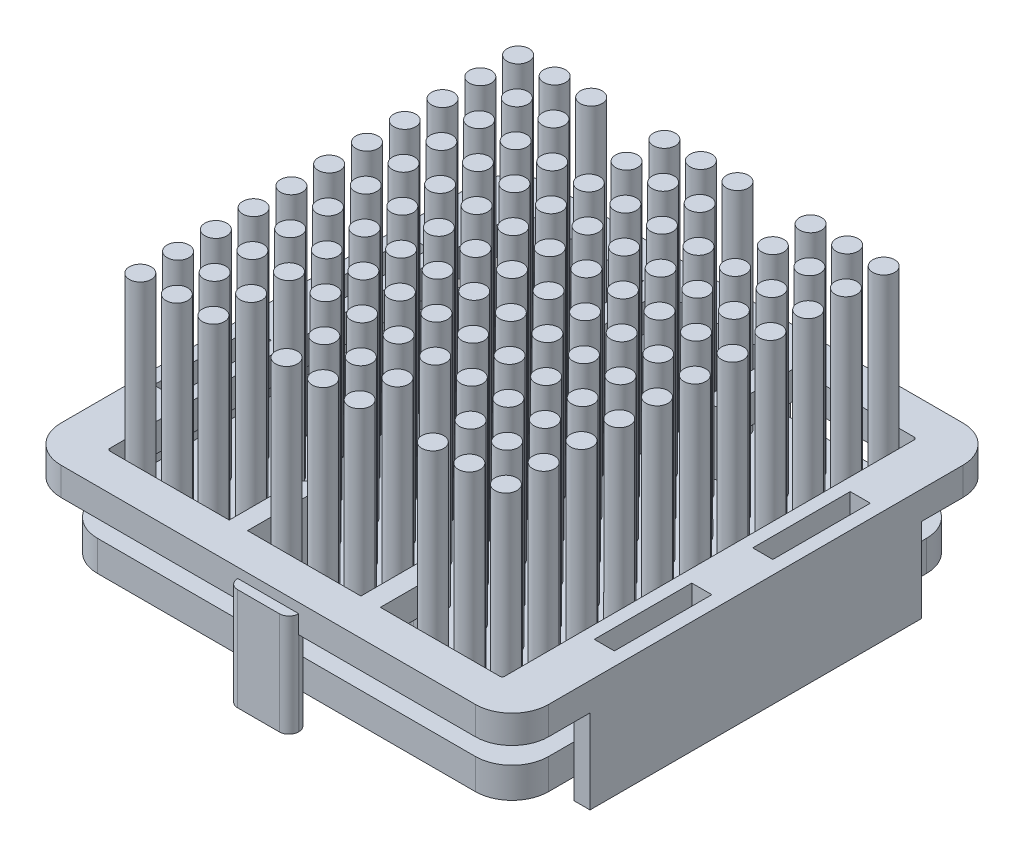
SolidWorks part; units mm, degrees
ref_plane "Alzado" through (0, 0, 0) normal (0, 0, 1) x (1, 0, 0)
ref_plane "Planta" through (0, 0, 0) normal (0, 1, 0) x (1, 0, 0)
ref_plane "Vista lateral" through (0, 0, 0) normal (1, 0, 0) x (0, 0, -1)
sketch "Croquis1" plane through (0, 0, 0) normal (0, 1, 0) x (1, 0, 0)
  line L1 (-20, 20) -> (20, 20)
  line L2 (-20, 20) -> (-20, -20)
  line L3 (-20, -20) -> (20, -20)
  line L4 (20, 20) -> (20, -20)
  dimension "D1" = 40
  dimension "D2" = 40
  dimension "D3" = 20
  dimension "D4" = 20
extrude "Extruir1" add sketch "Croquis1" along normal blind 9.2
sketch "Croquis2" plane through (0, 9.2, 0) normal (0, 1, 0) x (1, 0, 0)
  line L0 (20, 20) -> (-20, 20) construction
  line L1 (-16.2, 17) -> (-6.2, 17)
  line L2 (-16.2, 17) -> (-16.2, -17)
  line L3 (-16.2, -17) -> (-6.2, -17)
  line L4 (16.2, 17) -> (16.2, -17)
  line L5 (-4.7, 17) -> (4.6, 17)
  line L6 (-6.2, 17) -> (-6.2, 11)
  line L8 (-4.7, 17) -> (-4.7, 11)
  line L9 (6.2, 17) -> (16.2, 17)
  line L10 (4.6, 17) -> (4.6, 11)
  line L12 (6.2, 17) -> (6.2, 11)
  line L13 (-6.2, 11) -> (-4.7, 11)
  line L14 (4.6, -11) -> (6.2, -11)
  line L15 (-6.2, -11) -> (-4.7, -11)
  line L16 (-4.7, -17) -> (4.6, -17)
  line L17 (-20, -20) -> (20, -20) construction
  line L18 (-6.2, -11) -> (-6.2, -17)
  line L19 (-4.7, -11) -> (-4.7, -17)
  line L20 (4.6, -11) -> (4.6, -17)
  line L21 (6.2, -11) -> (6.2, -17)
  line L22 (4.6, 11) -> (6.2, 11)
  line L23 (6.2, -17) -> (16.2, -17)
  dimension "D1" = 32.4
  dimension "D2" = 16.2
  dimension "D3" = 34
  dimension "D4" = 17
  dimension "D5" = 9.3
  dimension "D6" = 12.4
  dimension "D7" = 6.2
  dimension "D8" = 1.5
  dimension "D9" = 9
  dimension "D10" = 9
extrude "Cortar-Extruir1" cut sketch "Croquis2" against normal blind 16.2
fillet "Redondeo1" radius 3 4 edges at (20, 4.6, -20) (20, 4.6, 20) (-20, 4.6, 20) (-20, 4.6, -20)
fillet "Redondeo2" radius 0.2 4 edges at (-16.2, 4.6, -17) (16.2, 4.6, -17) (-16.2, 4.6, 17) (16.2, 4.6, 17)
sketch "Croquis3" plane through (-20, 0, 0) normal (-1, 0, 0) x (0, 0, 1)
  line L0 (-17, 9.2) -> (17, 9.2) construction
  line L1 (-24.4068, 6.9) -> (-13.6, 6.9)
  line L2 (-24.4068, 6.9) -> (-24.4068, -1.7629)
  line L3 (-24.4068, -1.7629) -> (-13.6, -1.7629)
  line L4 (-13.6, 6.9) -> (-13.6, -1.7629)
  line L5 (13.6, 6.9) -> (26.4688, 6.9)
  line L6 (13.6, 6.9) -> (13.6, -1.7629)
  line L7 (13.6, -1.7629) -> (26.4688, -1.7629)
  line L8 (26.4688, 6.9) -> (26.4688, -1.7629)
  dimension "D1" = 27.2
  dimension "D2" = 2.3
  dimension "D3" = 13.6
extrude "Cortar-Extruir2" cut sketch "Croquis3" against normal blind 58.2
sketch "Croquis4" plane through (0, 0, -20) normal (0, 0, -1) x (-1, 0, 0)
  line L0 (-20, 6.9) -> (-17, 6.9) construction
  line L1 (-18.7, 6.9) -> (-11.7389, 6.9)
  line L2 (-18.7, 6.9) -> (-18.7, -3.2782)
  line L3 (-18.7, -3.2782) -> (-11.7389, -3.2782)
  line L4 (18.7, 6.9) -> (18.7, -3.2782)
  line L5 (11.3622, -3.2782) -> (18.7, -3.2782)
  line L7 (-11.7389, 6.9) -> (-11.7389, -3.2782)
  line L9 (11.3622, 6.9) -> (11.3622, -3.2782)
  line L10 (11.3622, 6.9) -> (18.7, 6.9)
  dimension "D1" = 37.4
  dimension "D2" = 18.7
extrude "Cortar-Extruir3" cut sketch "Croquis4" against normal blind 58.2
fillet "Redondeo3" radius 0.7 16 edges at (4.6, 3.45, 13.6) (6.2, 3.45, 13.6) (6.2, 4.6, 11) (4.6, 4.6, 11) (-4.7, 3.45, 13.6) (-4.7, 4.6, 11) (-6.2, 4.6, 11) (-6.2, 3.45, 13.6) (-6.2, 4.6, -11) (-6.2, 3.45, -13.6) (-4.7, 3.45, -13.6) (-4.7, 4.6, -11) (4.6, 3.45, -13.6) (6.2, 3.45, -13.6) (4.6, 4.6, -11) (6.2, 4.6, -11)
ref_plane "Plano1" through (0, 1.5, 0) normal (0, -1, 0) x (1, 0, 0)
sketch "Croquis5" plane through (0, 1.5, 0) normal (0, -1, 0) x (1, 0, 0)
  line L1 (-18.5, 18.5) -> (18.5, 18.5)
  line L2 (-18.5, 18.5) -> (-18.5, -18.5)
  line L3 (-18.5, -18.5) -> (18.5, -18.5)
  line L4 (18.5, 18.5) -> (18.5, -18.5)
  dimension "D1" = 37
  dimension "D2" = 37
  dimension "D3" = 18.5
  dimension "D4" = 18.5
extrude "Extruir2" add sketch "Croquis5" against normal blind 2.5 separate body
fillet "Redondeo4" radius 3 4 edges at (18.5, 2.75, -18.5) (-18.5, 2.75, -18.5) (18.5, 2.75, 18.5) (-18.5, 2.75, 18.5)
sketch "Croquis6" plane through (0, 4, 0) normal (0, 1, 0) x (1, 0, 0)
  line L0 (0, 0) -> (-24.1439, 0) construction
  line L1 (0, 0) -> (0, -22.8603) construction
  circle A0 centre (0, 0) radius 0.9
  circle A1 centre (3, 0) radius 0.9
  circle A2 centre (6, 0) radius 0.9
  circle A3 centre (9, 0) radius 0.9
  circle A4 centre (12, 0) radius 0.9
  circle A5 centre (15, 0) radius 0.9
  circle A6 centre (0, 3.1) radius 0.9
  circle A7 centre (3, 3.1) radius 0.9
  circle A8 centre (6, 3.1) radius 0.9
  circle A9 centre (9, 3.1) radius 0.9
  circle A10 centre (12, 3.1) radius 0.9
  circle A11 centre (15, 3.1) radius 0.9
  circle A12 centre (0, 6.2) radius 0.9
  circle A13 centre (3, 6.2) radius 0.9
  circle A14 centre (6, 6.2) radius 0.9
  circle A15 centre (9, 6.2) radius 0.9
  circle A16 centre (12, 6.2) radius 0.9
  circle A17 centre (15, 6.2) radius 0.9
  circle A18 centre (0, 9.3) radius 0.9
  circle A19 centre (3, 9.3) radius 0.9
  circle A20 centre (6, 9.3) radius 0.9
  circle A21 centre (9, 9.3) radius 0.9
  circle A22 centre (12, 9.3) radius 0.9
  circle A23 centre (15, 9.3) radius 0.9
  circle A24 centre (0, 12.4) radius 0.9
  circle A25 centre (3, 12.4) radius 0.9
  circle A26 centre (-15, 15.5) radius 0.9
  circle A27 centre (9, 12.4) radius 0.9
  circle A28 centre (12, 12.4) radius 0.9
  circle A29 centre (15, 12.4) radius 0.9
  circle A30 centre (0, 15.5) radius 0.9
  circle A31 centre (3, 15.5) radius 0.9
  circle A32 centre (-12, 15.5) radius 0.9
  circle A33 centre (9, 15.5) radius 0.9
  circle A34 centre (12, 15.5) radius 0.9
  circle A35 centre (15, 15.5) radius 0.9
  circle A36 centre (6, 12.4) radius 0.9 [skipped]
  circle A37 centre (6, 15.5) radius 0.9 [skipped]
  circle A38 centre (-9, 15.5) radius 0.9
  circle A39 centre (-3, 15.5) radius 0.9
  circle A40 centre (-15, 12.4) radius 0.9
  circle A41 centre (-12, 12.4) radius 0.9
  circle A42 centre (-9, 12.4) radius 0.9
  circle A43 centre (-3, 12.4) radius 0.9
  circle A44 centre (-15, 9.3) radius 0.9
  circle A45 centre (-12, 9.3) radius 0.9
  circle A46 centre (-9, 9.3) radius 0.9
  circle A47 centre (-6, 9.3) radius 0.9
  circle A48 centre (-3, 9.3) radius 0.9
  circle A49 centre (-15, 6.2) radius 0.9
  circle A50 centre (-12, 6.2) radius 0.9
  circle A51 centre (-9, 6.2) radius 0.9
  circle A52 centre (-6, 6.2) radius 0.9
  circle A53 centre (-3, 6.2) radius 0.9
  circle A54 centre (-15, 3.1) radius 0.9
  circle A55 centre (-12, 3.1) radius 0.9
  circle A56 centre (-9, 3.1) radius 0.9
  circle A57 centre (-6, 3.1) radius 0.9
  circle A58 centre (-3, 3.1) radius 0.9
  circle A59 centre (-15, 0) radius 0.9
  circle A60 centre (-12, 0) radius 0.9
  circle A61 centre (-9, 0) radius 0.9
  circle A62 centre (-6, 0) radius 0.9
  circle A63 centre (-3, 0) radius 0.9
  circle A64 centre (-3, -3.1) radius 0.9
  circle A65 centre (-6, -3.1) radius 0.9
  circle A66 centre (-9, -3.1) radius 0.9
  circle A67 centre (-12, -3.1) radius 0.9
  circle A68 centre (-15, -3.1) radius 0.9
  circle A69 centre (-3, -6.2) radius 0.9
  circle A70 centre (-6, -6.2) radius 0.9
  circle A71 centre (-9, -6.2) radius 0.9
  circle A72 centre (-12, -6.2) radius 0.9
  circle A73 centre (-15, -6.2) radius 0.9
  circle A74 centre (-3, -9.3) radius 0.9
  circle A75 centre (-6, -9.3) radius 0.9
  circle A76 centre (-9, -9.3) radius 0.9
  circle A77 centre (-12, -9.3) radius 0.9
  circle A78 centre (-15, -9.3) radius 0.9
  circle A79 centre (-3, -12.4) radius 0.9
  circle A80 centre (-9, -12.4) radius 0.9
  circle A81 centre (-12, -12.4) radius 0.9
  circle A82 centre (-15, -12.4) radius 0.9
  circle A83 centre (-3, -15.5) radius 0.9
  circle A84 centre (-9, -15.5) radius 0.9
  circle A85 centre (15, -15.5) radius 0.9
  circle A86 centre (12, -15.5) radius 0.9
  circle A87 centre (9, -15.5) radius 0.9
  circle A88 centre (-12, -15.5) radius 0.9
  circle A89 centre (3, -15.5) radius 0.9
  circle A90 centre (0, -15.5) radius 0.9
  circle A91 centre (15, -12.4) radius 0.9
  circle A92 centre (12, -12.4) radius 0.9
  circle A93 centre (9, -12.4) radius 0.9
  circle A94 centre (-15, -15.5) radius 0.9
  circle A95 centre (3, -12.4) radius 0.9
  circle A96 centre (0, -12.4) radius 0.9
  circle A97 centre (15, -9.3) radius 0.9
  circle A98 centre (12, -9.3) radius 0.9
  circle A99 centre (9, -9.3) radius 0.9
  circle A100 centre (6, -9.3) radius 0.9
  circle A101 centre (3, -9.3) radius 0.9
  circle A102 centre (0, -9.3) radius 0.9
  circle A103 centre (15, -6.2) radius 0.9
  circle A104 centre (12, -6.2) radius 0.9
  circle A105 centre (9, -6.2) radius 0.9
  circle A106 centre (6, -6.2) radius 0.9
  circle A107 centre (3, -6.2) radius 0.9
  circle A108 centre (0, -6.2) radius 0.9
  circle A109 centre (15, -3.1) radius 0.9
  circle A110 centre (12, -3.1) radius 0.9
  circle A111 centre (9, -3.1) radius 0.9
  circle A112 centre (6, -3.1) radius 0.9
  circle A113 centre (3, -3.1) radius 0.9
  circle A114 centre (0, -3.1) radius 0.9
  dimension "D1" = 1.8
extrude "Extruir3" add sketch "Croquis6" along normal offset from surface (17.6 mm away) 12.4 separate body up to face at (-0.0188, 9.2, 0) offset beyond the face yes
combine bodies "Combinar1" operation type add bodies to combine 203 201 199 197 136 134 132 130 195 193 191 189 128 126 124 122 187 185 183 181 120 118 116 114 179 177 175 173 112 110 108 106 105 171 169 167 165 163 161 159
sketch "Croquis7" plane through (0, 9.2, 0) normal (0, 1, 0) x (1, 0, 0)
  line L1 (17.25, 10.5) -> (18.9, 10.5)
  line L2 (17.25, 10.5) -> (17.25, 2.5)
  line L3 (17.25, 2.5) -> (18.9, 2.5)
  line L4 (18.9, 10.5) -> (18.9, 2.5)
  line L5 (17.25, -2.5) -> (18.9, -2.5)
  line L6 (17.25, -2.5) -> (17.25, -10.5)
  line L7 (17.25, -10.5) -> (18.9, -10.5)
  line L8 (18.9, -2.5) -> (18.9, -10.5)
  line L9 (0, 0) -> (0, -23.8606) construction
  line L10 (-18.9, -2.5) -> (-18.9, -10.5)
  line L11 (-17.25, -10.5) -> (-18.9, -10.5)
  line L12 (-17.25, -2.5) -> (-17.25, -10.5)
  line L13 (-17.25, -2.5) -> (-18.9, -2.5)
  line L14 (-18.9, 10.5) -> (-18.9, 2.5)
  line L15 (-17.25, 2.5) -> (-18.9, 2.5)
  line L16 (-17.25, 10.5) -> (-17.25, 2.5)
  line L17 (-17.25, 10.5) -> (-18.9, 10.5)
  dimension "D1" = 5
  dimension "D2" = 21
  dimension "D3" = 2.5
  dimension "D4" = 17.25
  dimension "D5" = 18.9
  dimension "D6" = 10.5
extrude "Cortar-Extruir4" cut sketch "Croquis7" against normal blind 12.4
sketch "Croquis8" plane through (0, 0, 0) normal (0, -1, 0) x (1, 0, 0)
  line L0 (-17, 20) -> (17, 20) construction
  line L1 (-1.71, 20.8) -> (1.71, 20.8)
  line L2 (-2.5, 20.01) -> (-2.5, 19.99)
  line L3 (-1.71, 19.2) -> (1.71, 19.2)
  line L4 (2.5, 20.01) -> (2.5, 19.99)
  line L5 (0, 0) -> (-28.2385, 0) construction
  line L6 (2.5, -20.01) -> (2.5, -19.99)
  line L7 (-1.71, -19.2) -> (1.71, -19.2)
  line L8 (-2.5, -20.01) -> (-2.5, -19.99)
  line L9 (-1.71, -20.8) -> (1.71, -20.8)
  arc A0 (-1.71, 20.8) -> (-2.5, 20.01) centre (-1.71, 20.01) ccw
  arc A1 (1.71, 20.8) -> (2.5, 20.01) centre (1.71, 20.01) cw
  arc A2 (1.71, 19.2) -> (2.5, 19.99) centre (1.71, 19.99) ccw
  arc A3 (-2.5, 19.99) -> (-1.71, 19.2) centre (-1.71, 19.99) ccw
  arc A4 (-2.5, -19.99) -> (-1.71, -19.2) centre (-1.71, -19.99) cw
  arc A5 (1.71, -19.2) -> (2.5, -19.99) centre (1.71, -19.99) cw
  arc A6 (1.71, -20.8) -> (2.5, -20.01) centre (1.71, -20.01) ccw
  arc A7 (-1.71, -20.8) -> (-2.5, -20.01) centre (-1.71, -20.01) cw
  point P9 (-2.5, 20.8)
  point P12 (2.5, 20.8)
  dimension "D5" = 0.79
  dimension "D1" = 1.6
  dimension "D2" = 5
  dimension "D3" = 2.5
  dimension "D4" = 0.8
extrude "Extruir4" add sketch "Croquis8" against normal blind 8.4 separate body
combine bodies "Combinar2" operation type add bodies to combine 220 222 223
